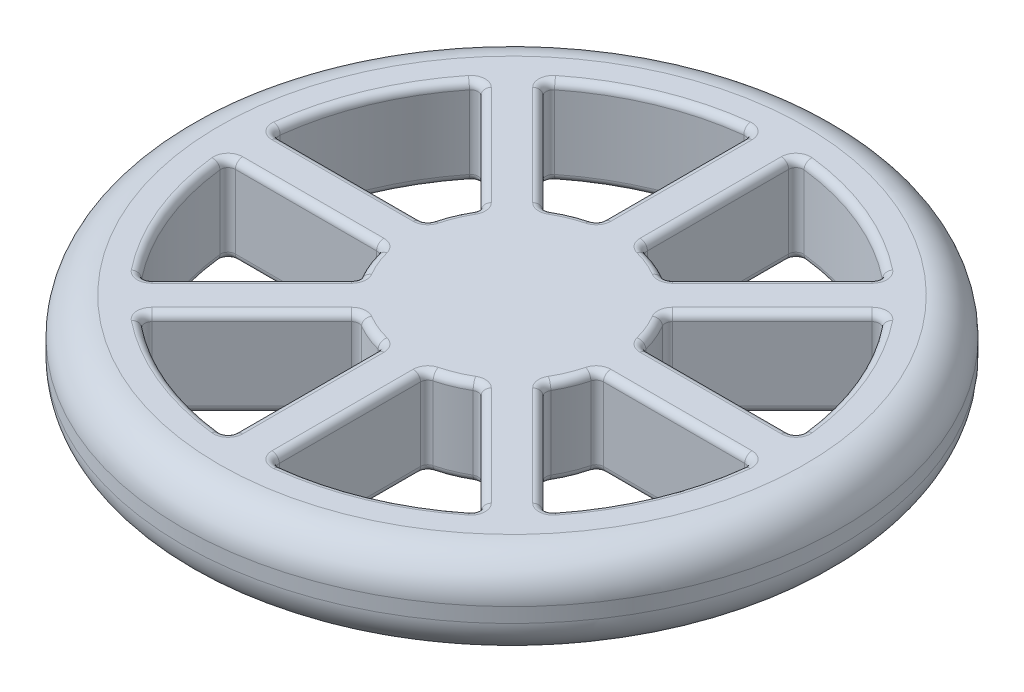
SolidWorks part; units mm, degrees
ref_plane "Front Plane" through (0, 0, 0) normal (0, 0, 1) x (1, 0, 0)
ref_plane "Top Plane" through (0, 0, 0) normal (0, 1, 0) x (1, 0, 0)
ref_plane "Right Plane" through (0, 0, 0) normal (1, 0, 0) x (0, 0, -1)
sketch "Sketch1" plane through (0, 0, 0) normal (0, 1, 0) x (1, 0, 0)
  circle A0 centre (0, 0) radius 22.5
  dimension "D1" = 45
extrude "Boss-Extrude1" add sketch "Sketch1" along normal blind 3 and the other way blind 3
fillet "Fillet1" radius 2.5 2 edges at (0, -3, 22.5) (0, 3, 22.5)
sketch "Sketch2" plane through (0, -3, 0) normal (0, -1, 0) x (1, 0, 0)
  line L1 (1.5, 17.9374) -> (1.5, 7.3485)
  line L3 (4.1355, 6.2568) -> (11.623, 13.7443)
  arc A3 (4.1355, 6.2568) -> (1.5, 7.3485) centre (0, 0) ccw
  arc A4 (11.623, 13.7443) -> (1.5, 17.9374) centre (0, 0) ccw
extrude "Cut-Extrude1" cut sketch "Sketch2" against normal up to next
fillet "Fillet2" radius 0.5 12 edges at (1.5, 0, 7.3485) (4.1355, 0, 6.2568) (11.623, 0, 13.7443) (1.5, 0, 17.9374) (1.5, 3, 12.6429) (2.8701, 3, 6.9291) (6.8883, 3, 16.6298) (7.8792, 3, 10.0006) (7.8792, -3, 10.0006) (2.8701, -3, 6.9291) (6.8883, -3, 16.6298) (1.5, -3, 12.6429)
sketch "Sketch3" [suppressed] plane through (0, 0, 0) normal (1, 0, 0) x (0, 0, -1)
  line L0 (0, 3) -> (0, -7.3813) construction
  line L1 (19.5, 3) -> (-19.5, 3) construction
pattern_circular "CirPattern1" count 8 over 360 about axis through (0, 3, 0) along (0, -1, 0) of "Cut-Extrude1", "Fillet2" reverse direction yes
